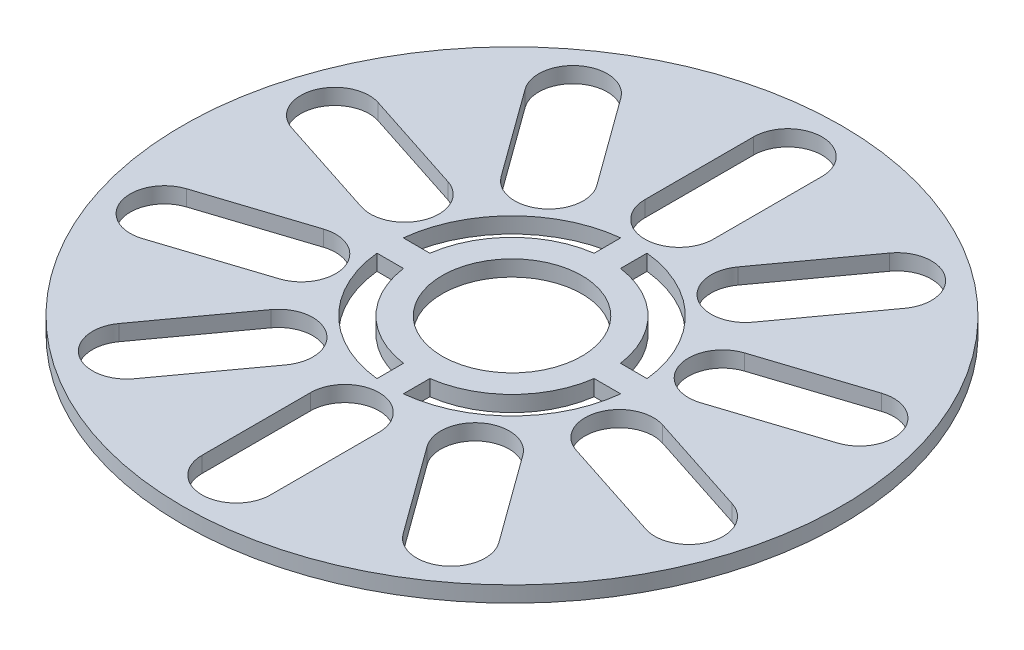
SolidWorks part; units mm, degrees
ref_plane "Front Plane" through (0, 0, 0) normal (0, 0, 1) x (1, 0, 0)
ref_plane "Top Plane" through (0, 0, 0) normal (0, 1, 0) x (1, 0, 0)
ref_plane "Right Plane" through (0, 0, 0) normal (1, 0, 0) x (0, 0, -1)
sketch "Sketch1" plane through (0, 0, 0) normal (0, 1, 0) x (1, 0, 0)
  line L0 (-2.5, 18.078) -> (-2.5, 23.1152)
  line L1 (2.5, 18.078) -> (2.5, 23.1152)
  line L2 (18.078, 2.5) -> (23.1152, 2.5)
  line L3 (18.078, -2.5) -> (23.1152, -2.5)
  line L4 (2.5, -18.078) -> (2.5, -23.1152)
  line L5 (-2.5, -18.078) -> (-2.5, -23.1152)
  line L6 (-18.078, -2.5) -> (-23.1152, -2.5)
  line L7 (-18.078, 2.5) -> (-23.1152, 2.5)
  line L8 (0, 31.7) -> (0, 52.3) construction
  line L9 (-6.5, 31.7) -> (-6.5, 52.3)
  line L10 (6.5, 31.7) -> (6.5, 52.3)
  line L11 (23.8914, 21.8252) -> (35.9998, 38.491)
  line L12 (13.3742, 29.4664) -> (25.4826, 46.1322)
  line L13 (18.6328, 25.6458) -> (30.7412, 42.3116) construction
  line L14 (32.1571, 3.614) -> (51.7489, 9.9797)
  line L15 (28.1399, 15.9777) -> (47.7316, 22.3435)
  line L16 (30.1485, 9.7958) -> (49.7403, 16.1616) construction
  line L17 (28.1399, -15.9777) -> (47.7316, -22.3435)
  line L18 (32.1571, -3.614) -> (51.7489, -9.9797)
  line L19 (30.1485, -9.7958) -> (49.7403, -16.1616) construction
  line L20 (13.3742, -29.4664) -> (25.4826, -46.1322)
  line L21 (23.8914, -21.8252) -> (35.9998, -38.491)
  line L22 (18.6328, -25.6458) -> (30.7412, -42.3116) construction
  line L23 (-6.5, -31.7) -> (-6.5, -52.3)
  line L24 (6.5, -31.7) -> (6.5, -52.3)
  line L25 (0, -31.7) -> (0, -52.3) construction
  line L26 (-23.8914, -21.8252) -> (-35.9998, -38.491)
  line L27 (-13.3742, -29.4664) -> (-25.4826, -46.1322)
  line L28 (-18.6328, -25.6458) -> (-30.7412, -42.3116) construction
  line L29 (-32.1571, -3.614) -> (-51.7489, -9.9797)
  line L30 (-28.1399, -15.9777) -> (-47.7316, -22.3435)
  line L31 (-30.1485, -9.7958) -> (-49.7403, -16.1616) construction
  line L32 (-28.1399, 15.9777) -> (-47.7316, 22.3435)
  line L33 (-32.1571, 3.614) -> (-51.7489, 9.9797)
  line L34 (-30.1485, 9.7958) -> (-49.7403, 16.1616) construction
  line L35 (-13.3742, 29.4664) -> (-25.4826, 46.1322)
  line L36 (-23.8914, 21.8252) -> (-35.9998, 38.491)
  line L37 (-18.6328, 25.6458) -> (-30.7412, 42.3116) construction
  circle A1 centre (0, 0) radius 13.25
  arc A2 (-2.5, 23.1152) -> (-23.1152, 2.5) centre (0, 0) ccw
  arc A3 (-2.5, 18.078) -> (-18.078, 2.5) centre (0, 0) ccw
  circle A4 centre (0, 0) radius 62.5
  arc A5 (18.078, 2.5) -> (2.5, 18.078) centre (0, 0) ccw
  arc A6 (23.1152, 2.5) -> (2.5, 23.1152) centre (0, 0) ccw
  arc A7 (2.5, -18.078) -> (18.078, -2.5) centre (0, 0) ccw
  arc A8 (2.5, -23.1152) -> (23.1152, -2.5) centre (0, 0) ccw
  arc A9 (-23.1152, -2.5) -> (-2.5, -23.1152) centre (0, 0) ccw
  arc A10 (-18.078, -2.5) -> (-2.5, -18.078) centre (0, 0) ccw
  arc A11 (-6.5, 31.7) -> (6.5, 31.7) centre (0, 31.7) ccw
  arc A12 (6.5, 52.3) -> (-6.5, 52.3) centre (0, 52.3) ccw
  arc A13 (13.3742, 29.4664) -> (23.8914, 21.8252) centre (18.6328, 25.6458) ccw
  arc A14 (35.9998, 38.491) -> (25.4826, 46.1322) centre (30.7412, 42.3116) ccw
  arc A15 (28.1399, 15.9777) -> (32.1571, 3.614) centre (30.1485, 9.7958) ccw
  arc A16 (51.7489, 9.9797) -> (47.7316, 22.3435) centre (49.7403, 16.1616) ccw
  arc A17 (32.1571, -3.614) -> (28.1399, -15.9777) centre (30.1485, -9.7958) ccw
  arc A18 (47.7316, -22.3435) -> (51.7489, -9.9797) centre (49.7403, -16.1616) ccw
  arc A19 (23.8914, -21.8252) -> (13.3742, -29.4664) centre (18.6328, -25.6458) ccw
  arc A20 (25.4826, -46.1322) -> (35.9998, -38.491) centre (30.7412, -42.3116) ccw
  arc A21 (6.5, -31.7) -> (-6.5, -31.7) centre (0, -31.7) ccw
  arc A22 (-6.5, -52.3) -> (6.5, -52.3) centre (0, -52.3) ccw
  arc A23 (-13.3742, -29.4664) -> (-23.8914, -21.8252) centre (-18.6328, -25.6458) ccw
  arc A24 (-35.9998, -38.491) -> (-25.4826, -46.1322) centre (-30.7412, -42.3116) ccw
  arc A25 (-28.1399, -15.9777) -> (-32.1571, -3.614) centre (-30.1485, -9.7958) ccw
  arc A26 (-51.7489, -9.9797) -> (-47.7316, -22.3435) centre (-49.7403, -16.1616) ccw
  arc A27 (-32.1571, 3.614) -> (-28.1399, 15.9777) centre (-30.1485, 9.7958) ccw
  arc A28 (-47.7316, 22.3435) -> (-51.7489, 9.9797) centre (-49.7403, 16.1616) ccw
  arc A29 (-23.8914, 21.8252) -> (-13.3742, 29.4664) centre (-18.6328, 25.6458) ccw
  arc A30 (-25.4826, 46.1322) -> (-35.9998, 38.491) centre (-30.7412, 42.3116) ccw
  point P10 (0, 42)
  point P25 (0, 0)
  point P33 (24.687, 33.9787)
  point P40 (39.9444, 12.9787)
  point P47 (39.9444, -12.9787)
  point P54 (24.687, -33.9787)
  point P61 (0, -42)
  point P68 (-24.687, -33.9787)
  point P75 (-39.9444, -12.9787)
  point P82 (-39.9444, 12.9787)
  point P89 (-24.687, 33.9787)
  point P94 (0, 0)
  dimension "D1" = 125
  dimension "D2" = 26.5
  dimension "D3" = 46.5
  dimension "D4" = 36.5
  dimension "D10" = 6.5
  dimension "D5" = 5
  dimension "D6" = 2.5
  dimension "D8" = 42
  dimension "D9" = 20.6
  dimension "D7" = 4
  dimension "D11" = 10
extrude "Boss-Extrude1" add sketch "Sketch1" along normal blind 3
sketch "Sketch3" plane through (0, 3, 0) normal (0, 1, 0) x (1, 0, 0)
  circle A0 centre (0, 0) radius 20.75
  circle A1 centre (0, 42) radius 6.5
  arc A2 (-6.5, 31.7) -> (6.5, 31.7) centre (0, 31.7) ccw construction
  circle A3 centre (0, -42) radius 6.5
  arc A4 (6.5, -31.7) -> (-6.5, -31.7) centre (0, -31.7) ccw construction
  dimension "D1" = 41.5
  dimension "D2" = 13
  dimension "D4" = 10.3
  dimension "D3" = 10.3
